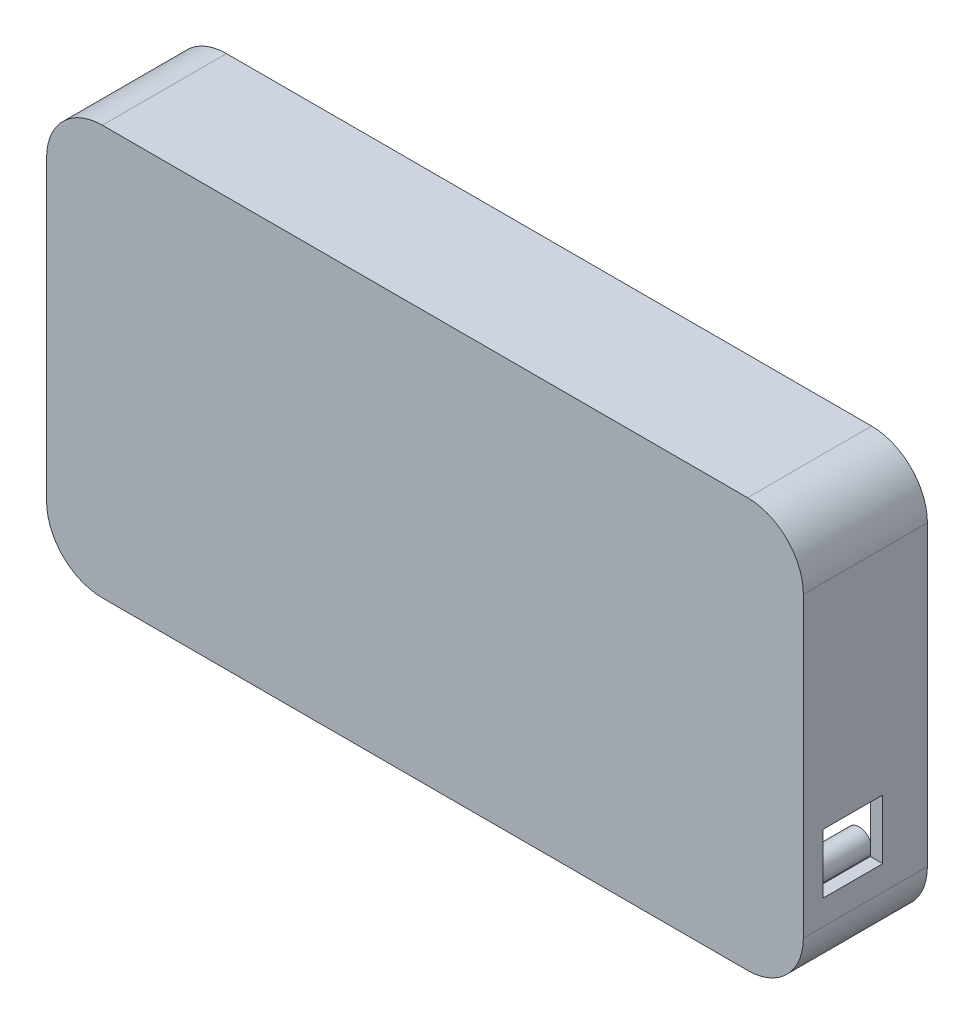
SolidWorks part; units mm, degrees
material "交联聚乙烯"
ref_plane "前视基准面" through (0, 0, 0) normal (0, 0, 1) x (1, 0, 0)
ref_plane "上视基准面" through (0, 0, 0) normal (0, 1, 0) x (1, 0, 0)
ref_plane "右视基准面" through (0, 0, 0) normal (1, 0, 0) x (0, 0, -1)
sketch "草图1" plane through (0, 0, 0) normal (0, 0, 1) x (1, 0, 0)
  line L1 (-130, 82.5) -> (130, 82.5)
  line L2 (-152.5, 60) -> (-152.5, -60)
  line L3 (-130, -82.5) -> (130, -82.5)
  line L4 (152.5, 60) -> (152.5, -60)
  line L5 (0, -82.5) -> (0, 82.5) construction
  line L6 (-152.5, 0) -> (152.5, 0) construction
  line L14 (-130, 77.5) -> (130, 77.5)
  line L15 (147.5, 60) -> (147.5, -60)
  line L16 (-130, -77.5) -> (130, -77.5)
  line L17 (-147.5, 60) -> (-147.5, -60)
  line L18 (-150.2, 60) -> (-150.2, -60)
  line L19 (-130, -80.2) -> (130, -80.2)
  line L20 (150.2, 60) -> (150.2, -60)
  line L21 (-130, 80.2) -> (130, 80.2)
  arc A0 (-130, -82.5) -> (-152.5, -60) centre (-130, -60) cw
  arc A1 (130, -82.5) -> (152.5, -60) centre (130, -60) ccw
  arc A2 (152.5, 60) -> (130, 82.5) centre (130, 60) ccw
  arc A3 (-152.5, 60) -> (-130, 82.5) centre (-130, 60) cw
  arc A12 (147.5, 60) -> (130, 77.5) centre (130, 60) ccw
  arc A13 (130, -77.5) -> (147.5, -60) centre (130, -60) ccw
  arc A14 (-130, -77.5) -> (-147.5, -60) centre (-130, -60) cw
  arc A15 (-147.5, 60) -> (-130, 77.5) centre (-130, 60) cw
  circle A16 centre (130, 60) radius 2.6
  circle A17 centre (130, 60) radius 5.1
  circle A18 centre (130, -60) radius 2.6
  circle A19 centre (130, -60) radius 5.1
  circle A20 centre (-130, 60) radius 2.6
  circle A21 centre (-130, 60) radius 5.1
  circle A22 centre (-130, -60) radius 2.6
  circle A23 centre (-130, -60) radius 5.1
  arc A24 (-130, -80.2) -> (-150.2, -60) centre (-130, -60) cw
  arc A25 (130, -80.2) -> (150.2, -60) centre (130, -60) ccw
  arc A26 (150.2, 60) -> (130, 80.2) centre (130, 60) ccw
  arc A27 (-150.2, 60) -> (-130, 80.2) centre (-130, 60) cw
  point P0 (0, 0)
  point P6 (-152.5, -82.5)
  point P9 (152.5, -82.5)
  point P12 (152.5, 82.5)
  dimension "D3" = 22.5
  dimension "D6" = 5.2
  dimension "D8" = 5.2
  dimension "D10" = 5.2
  dimension "D12" = 5.2
  dimension "D1" = 305
  dimension "D2" = 165
  dimension "D4" = 2.3
  dimension "D7" = 2.5
  dimension "D9" = 2.5
  dimension "D11" = 2.5
  dimension "D13" = 2.5
extrude "凸台-拉伸1" add sketch "草图1" along normal blind 50 contours A0 L2 A3 L1 A2 L4 A1 L3
extrude "切除-拉伸1" cut sketch "草图1<4>" along normal blind 45 contours A15 L17 A14 L16 A13 L15 A12 L14 region at (0, 0, 0)
sketch "草图1<4>" plane through (0, 0, 0) normal (0, 0, 1) x (1, 0, 0) same geometry as "草图1"
sketch "草图3" plane through (0, 0, 0) normal (0, 0, -1) x (-1, 0, 0)
extrude "切除-拉伸2" cut sketch "草图1<5>" along normal blind 5 contours A27 L21 A26 L20 A25 L19 A24 L18 L17 A15 L14 A12 L15 A13 L16 A14 region at (-144.0428, 74.0428, 0)
sketch "草图1<5>" plane through (0, 0, 0) normal (0, 0, 1) x (1, 0, 0) same geometry as "草图1"
extrude "切除-拉伸3" cut sketch "草图1<6>" along normal blind 5 contours A23 | A21 | A17 | A19
sketch "草图1<6>" plane through (0, 0, 0) normal (0, 0, 1) x (1, 0, 0) same geometry as "草图1"
extrude "切除-拉伸4" cut sketch "草图1<7>" along normal blind 25 contours A22 | A16 | A18 | A20 region at (130, 60, 0) region at (130, -60, 0) region at (-130, -60, 0)
sketch "草图1<7>" plane through (0, 0, 0) normal (0, 0, 1) x (1, 0, 0) same geometry as "草图1"
sketch3d "3D草图1"
  point P0 (44.0813, -82.5, 36.7135)
sketch "草图14" plane through (0, -82.5, 0) normal (0, -1, 0) x (1, 0, 0)
  line L0 (-130, 45) -> (130, 45) construction
  line L5 (-80, 38) -> (-70.9, 38) construction
  line L6 (-130, 50) -> (-130, 0) construction
  line L8 (-87, 33.5) -> (-73, 33.5)
  line L9 (-87, 33.5) -> (-87, 42.5)
  line L10 (-87, 42.5) -> (-73, 42.5)
  line L11 (-73, 33.5) -> (-73, 42.5)
  line L12 (-80, 42.5) -> (-80, 33.5) construction
  line L13 (-87, 38) -> (-73, 38) construction
  line L14 (-87, 33.5) -> (-73, 33.5)
  line L15 (-87, 42.5) -> (-73, 42.5)
  line L16 (0, 45) -> (0, 33.2265) construction
  circle A0 centre (-70.9, 38) radius 1.6
  circle A2 centre (-89.1, 38) radius 1.6
  point P0 (-80, 38)
  dimension "D5" = 3.2
  dimension "D1" = 14
  dimension "D2" = 9
  dimension "D3" = 7
  dimension "D4" = 9.1
  dimension "D6" = 50
extrude "USB口" cut sketch "草图14" against normal blind 5 contours L8 L11 L10 L9 | A2 | A0 region at (-80, -82.5, 38) region at (-89.1, -82.5, 38)
sketch "草图16" plane through (152.5, 0, 0) normal (1, 0, 0) x (0, 0, -1)
  line L1 (-50, 60) -> (-50, -60) construction
  line L3 (-42, -26) -> (-18, -26)
  line L4 (-42, -26) -> (-42, -50)
  line L5 (-42, -50) -> (-18, -50)
  line L6 (-18, -26) -> (-18, -50)
  line L7 (-30, -50) -> (-30, -26) construction
  line L8 (-42, -38) -> (-18, -38) construction
  line L9 (-50, -60) -> (0, -60) construction
  point P0 (-30, -38)
  dimension "D1" = 24
  dimension "D2" = 24
  dimension "D3" = 10
  dimension "D4" = 20
extrude "切除-拉伸12" cut sketch "草图16" against normal blind 5
sketch "草图18" plane through (-152.5, 0, 0) normal (-1, 0, 0) x (0, 0, 1)
  line L1 (50, 60) -> (50, -60) construction
  line L3 (50, -60) -> (0, -60) construction
  line L4 (18, -26) -> (42, -26)
  line L5 (18, -26) -> (18, -50)
  line L6 (18, -50) -> (42, -50)
  line L7 (42, -26) -> (42, -50)
  line L8 (30, -50) -> (30, -26) construction
  line L9 (18, -38) -> (42, -38) construction
  point P4 (30, -38)
  dimension "D1" = 24
  dimension "D2" = 24
  dimension "D3" = 10
  dimension "D4" = 20
extrude "切除-拉伸13" cut sketch "草图18" against normal blind 5
sketch "草图19" plane through (0, 0, 45) normal (0, 0, -1) x (-1, 0, 0)
  line L0 (-103, 36) -> (-18, 36) construction
  line L1 (-103, 40) -> (-18, 40)
  line L2 (-103, 32) -> (-18, 32)
  line L3 (152.5, 0) -> (-152.5, 0) construction
  line L4 (0, -82.5) -> (0, 82.5) construction
  line L5 (-147.5, 0) -> (-107.2295, 0) construction
  line L6 (0, 77.5) -> (0, 61.8371) construction
  line L7 (103, 36) -> (18, 36) construction
  line L8 (103, 40) -> (18, 40)
  line L9 (103, 32) -> (18, 32)
  line L10 (-103, -24) -> (-23, -24) construction
  line L11 (-103, -20) -> (-23, -20)
  line L12 (-103, -28) -> (-23, -28)
  line L14 (103, -24) -> (23, -24) construction
  line L15 (103, -20) -> (23, -20)
  line L16 (103, -28) -> (23, -28)
  arc A0 (-103, 40) -> (-103, 32) centre (-103, 36) ccw
  arc A1 (-18, 32) -> (-18, 40) centre (-18, 36) ccw
  arc A2 (103, 40) -> (103, 32) centre (103, 36) cw
  arc A3 (18, 32) -> (18, 40) centre (18, 36) cw
  arc A4 (-103, -20) -> (-103, -28) centre (-103, -24) ccw
  arc A5 (-23, -28) -> (-23, -20) centre (-23, -24) ccw
  arc A6 (103, -20) -> (103, -28) centre (103, -24) cw
  arc A7 (23, -28) -> (23, -20) centre (23, -24) cw
  point P2 (-60.5, 36)
  point P13 (60.5, 36)
  point P23 (-63, -24)
  point P33 (63, -24)
  dimension "D2" = 4
  dimension "D7" = 4
  dimension "D8" = 80
  dimension "D1" = 85
  dimension "D3" = 18
  dimension "D4" = 32
  dimension "D5" = 23
  dimension "D6" = 20
extrude "凸台-拉伸2" add sketch "草图19" along normal blind 40
sketch "草图29" plane through (0, 0, 45) normal (0, 0, -1) x (-1, 0, 0)
  line L0 (14.35, -45.2) -> (-14.35, -45.2)
  line L1 (12.85, -43.7) -> (-12.85, -43.7)
  line L2 (12.85, -43.7) -> (12.85, -20)
  line L3 (12.85, -20) -> (-12.85, -20)
  line L4 (-12.85, -43.7) -> (-12.85, -20)
  line L5 (0, -20) -> (0, -43.7) construction
  line L6 (12.85, -31.85) -> (-12.85, -31.85) construction
  line L7 (0, -41.7182) -> (0, 1.1541) construction
  line L8 (-14.35, -45.2) -> (-14.35, -18.5)
  line L9 (14.35, -18.5) -> (-14.35, -18.5)
  line L10 (17.8546, 0) -> (-23.7773, 0) construction
  line L11 (14.35, -45.2) -> (14.35, -18.5)
  line L12 (0, -31.85) -> (-17.5, -31.85) construction
  line L13 (12.85, -20) -> (12.85, -18.5)
  line L14 (-30, 20) -> (30, 20) construction
  line L15 (-30, 20) -> (-30, -10) construction
  line L16 (-30, -10) -> (30, -10) construction
  line L17 (30, 20) -> (30, -10) construction
  line L18 (0, -10) -> (0, 20) construction
  line L19 (-30, 5) -> (30, 5) construction
  line L20 (-12.85, -20) -> (-12.85, -18.5)
  circle A0 centre (-17.5, -31.85) radius 1.15
  circle A1 centre (-17.5, -31.85) radius 2.85
  circle A2 centre (17.5, -31.85) radius 1.15
  circle A3 centre (17.5, -31.85) radius 2.85
  circle A4 centre (-30, 20) radius 1.2
  circle A5 centre (30, 20) radius 1.2
  circle A6 centre (30, -10) radius 1.2
  circle A7 centre (-30, -10) radius 1.2
  circle A8 centre (-30, 20) radius 3.4
  circle A9 centre (30, 20) radius 3.4
  circle A10 centre (30, -10) radius 3.4
  circle A11 centre (-30, -10) radius 3.4
  point P0 (0, -31.85)
  point P21 (0, 0)
  dimension "D6" = 2.3
  dimension "D10" = 2.4
  dimension "D11" = 2.4
  dimension "D12" = 2.4
  dimension "D13" = 2.4
  dimension "D1" = 23.7
  dimension "D2" = 25.7
  dimension "D3" = 20
  dimension "D5" = 17.5
  dimension "D8" = 60
  dimension "D9" = 30
  dimension "D15" = 5
  dimension "D4" = 1.5
  dimension "D7" = 1.7
  dimension "D14" = 2.2
extrude "凸台-拉伸3" add sketch "草图29" along normal blind 2 contours L0 L11 L9 L8 L1 L4 L3 L2 region at (0, -44.808, 45)
extrude "凸台-拉伸4" add sketch "草图29<4>" along normal blind 5 contours A1 A0 | A3 A2 region at (20.2694, -31.85, 45) region at (-14.7306, -31.85, 45)
sketch "草图29<4>" plane through (0, 0, 45) normal (0, 0, -1) x (-1, 0, 0) same geometry as "草图29"
extrude "凸台-拉伸5" add sketch "草图29<5>" along normal blind 6.5 contours A8 A4 | A11 A7 | A9 A5 | A10 A6 region at (33.3038, 20, 45) region at (-26.6962, 20, 45) region at (-26.6962, -10, 45) region at (33.3038, -10, 45)
sketch "草图29<5>" plane through (0, 0, 45) normal (0, 0, -1) x (-1, 0, 0) same geometry as "草图29"
extrude "切除-拉伸14" cut sketch "草图29<6>" against normal blind 2 contours A2 | A0 | A6 | A7 | A4 | A5 region at (17.5, -31.85, 45) region at (-17.5, -31.85, 45)
sketch "草图29<6>" plane through (0, 0, 45) normal (0, 0, -1) x (-1, 0, 0) same geometry as "草图29"
